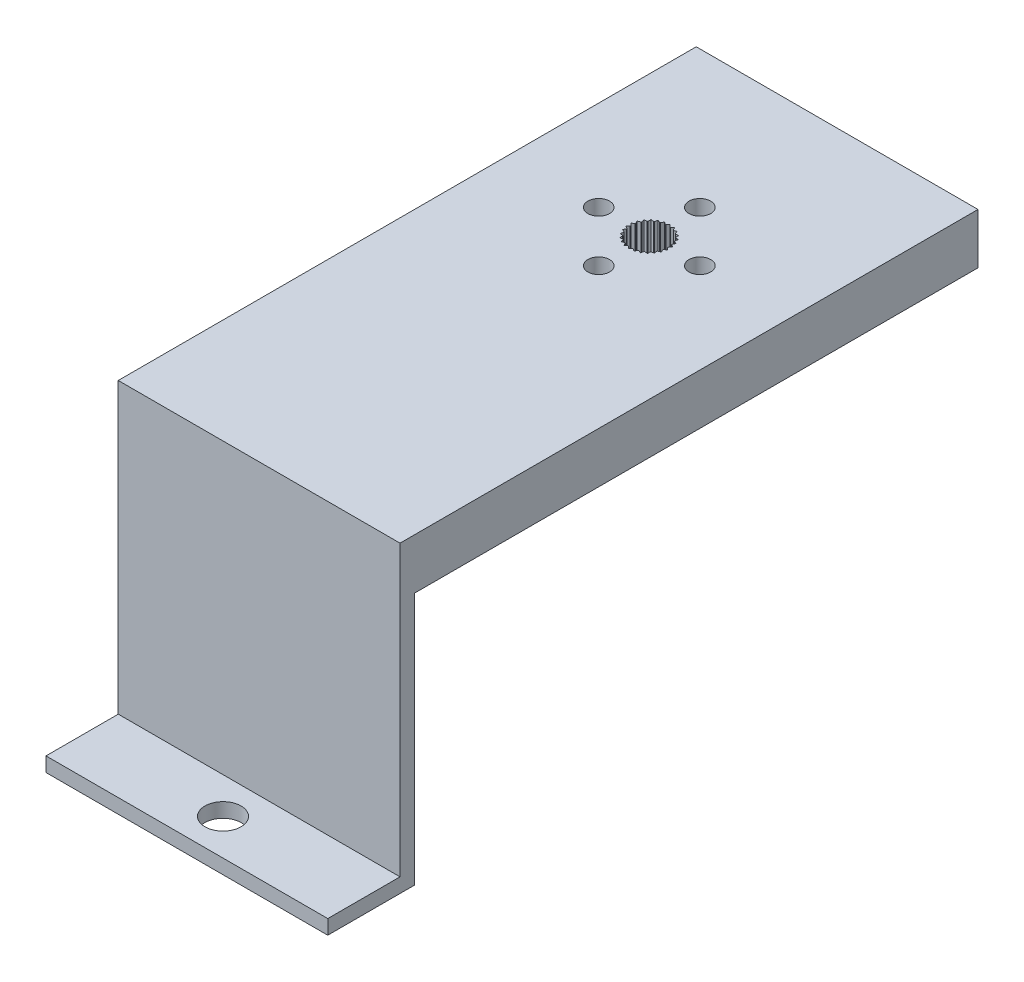
SolidWorks part; units mm, degrees
ref_plane "Front Plane" through (0, 0, 0) normal (0, 0, 1) x (1, 0, 0)
ref_plane "Top Plane" through (0, 0, 0) normal (0, 1, 0) x (1, 0, 0)
ref_plane "Right Plane" through (0, 0, 0) normal (1, 0, 0) x (0, 0, -1)
sketch "Sketch3" plane through (0, 0, 0) normal (1, 0, 0) x (0, 0, -1)
  line L0 (0, 38.5) -> (-60, 38.5)
  line L1 (0, 21.45) -> (0, -21.45) construction
  line L2 (-60, 38.5) -> (-60, 2)
  line L3 (-60, 2) -> (-70, 2)
  line L4 (-70, 2) -> (-70, 0)
  line L5 (21.45, 0) -> (-21.45, 0) construction
  line L6 (-70, 0) -> (-58, 0)
  line L7 (-58, 0) -> (-58, 36.5)
  line L8 (-58, 36.5) -> (0, 36.5)
  line L9 (0, 36.5) -> (0, 38.5)
  dimension "D1" = 70
  dimension "D2" = 38.5
  dimension "D3" = 10
  dimension "D4" = 2
  dimension "D5" = 2
  dimension "D6" = 2
extrude "Boss-Extrude1" add sketch "Sketch3" along normal mid plane 39 contours L2 L3 L4 L6 L7 L8 L9 L0
sketch "Sketch5" plane through (0, 0, 0) normal (0, 1, 0) x (1, 0, 0)
  line L0 (19.5, -58) -> (19.5, 0) construction
  line L1 (0.694, -3.1843) -> (0.3638, -3.4256)
  line L2 (0, -3.1) -> (-0.2629, -3.4133)
  line L3 (0, -3.1) -> (0.2629, -3.4133)
  line L4 (0.694, -3.1843) -> (0.8743, -3.5514)
  line L5 (1.3477, -3.4322) -> (0.9693, -3.5874)
  line L6 (1.3477, -3.4322) -> (1.4349, -3.8318)
  line L7 (1.9231, -3.8293) -> (1.5185, -3.8895)
  line L8 (1.9231, -3.8293) -> (1.9121, -4.2382)
  line L9 (2.3867, -4.3526) -> (1.9794, -4.3142)
  line L10 (2.3867, -4.3526) -> (2.2781, -4.747)
  line L11 (2.7115, -4.9716) -> (2.3254, -4.8369)
  line L12 (2.7115, -4.9716) -> (2.5118, -5.3286)
  line L13 (2.8789, -5.6504) -> (2.5361, -5.4272)
  line L14 (2.8789, -5.6504) -> (2.5995, -5.9492)
  line L15 (2.8789, -6.3496) -> (2.5995, -6.0508)
  line L16 (2.8789, -6.3496) -> (2.5361, -6.5728)
  line L17 (2.7115, -7.0284) -> (2.5118, -6.6714)
  line L18 (2.7115, -7.0284) -> (2.3254, -7.1631)
  line L19 (2.3867, -7.6474) -> (2.2781, -7.253)
  line L20 (2.3867, -7.6474) -> (1.9794, -7.6858)
  line L21 (1.9231, -8.1707) -> (1.9121, -7.7618)
  line L22 (1.9231, -8.1707) -> (1.5185, -8.1105)
  line L23 (1.3477, -8.5678) -> (1.4349, -8.1682)
  line L24 (1.3477, -8.5678) -> (0.9693, -8.4126)
  line L25 (0.694, -8.8157) -> (0.8743, -8.4486)
  line L26 (0.694, -8.8157) -> (0.3638, -8.5744)
  line L27 (0, -8.9) -> (0.2629, -8.5867)
  line L28 (0, -8.9) -> (-0.2629, -8.5867)
  line L29 (-0.694, -8.8157) -> (-0.3638, -8.5744)
  line L30 (-0.694, -8.8157) -> (-0.8743, -8.4486)
  line L31 (-1.3477, -8.5678) -> (-0.9693, -8.4126)
  line L32 (-1.3477, -8.5678) -> (-1.4349, -8.1682)
  line L33 (-1.9231, -8.1707) -> (-1.5185, -8.1105)
  line L34 (-1.9231, -8.1707) -> (-1.9121, -7.7618)
  line L35 (-2.3867, -7.6474) -> (-1.9794, -7.6858)
  line L36 (-2.3867, -7.6474) -> (-2.2781, -7.253)
  line L37 (-2.7115, -7.0284) -> (-2.3254, -7.1631)
  line L38 (-2.7115, -7.0284) -> (-2.5118, -6.6714)
  line L39 (-2.8789, -6.3496) -> (-2.5361, -6.5728)
  line L40 (-2.8789, -6.3496) -> (-2.5995, -6.0508)
  line L41 (-2.8789, -5.6504) -> (-2.5995, -5.9492)
  line L42 (-2.8789, -5.6504) -> (-2.5361, -5.4272)
  line L43 (-2.7115, -4.9716) -> (-2.5118, -5.3286)
  line L44 (-2.7115, -4.9716) -> (-2.3254, -4.8369)
  line L45 (-2.3867, -4.3526) -> (-2.2781, -4.747)
  line L46 (-2.3867, -4.3526) -> (-1.9794, -4.3142)
  line L47 (-1.9231, -3.8293) -> (-1.9121, -4.2382)
  line L48 (-1.9231, -3.8293) -> (-1.5185, -3.8895)
  line L49 (-1.3477, -3.4322) -> (-1.4349, -3.8318)
  line L50 (-1.3477, -3.4322) -> (-0.9693, -3.5874)
  line L51 (-0.694, -3.1843) -> (-0.8743, -3.5514)
  line L52 (-0.694, -3.1843) -> (-0.3638, -3.4256)
  arc A0 (-0.2629, -3.4133) -> (0.2629, -3.4133) centre (0, -6) ccw
  point P81 (0, -6)
  dimension "D1" = 5.2
  dimension "D2" = 6
  dimension "D3" = 19.5
  dimension "D4" = 26
extrude "Cut-Extrude2" cut sketch "Sketch5" along normal blind 40 contours A0 L3 L2 | A0 L52 L51 | A0 L50 L49 | A0 L48 L47 | A0 L46 L45 | A0 L44 L43 | A0 L42 L41 | A0 L40 L39 | A0 L38 L37 | A0 L36 L35 | A0 L34 L33 | A0 L32 L31 | A0 L30 L29 | A0 L28 L27 | A0 L26 L25 | A0 L24 L23 | A0 L22 L21 | A0 L20 L19 | A0 L18 L17 | A0 L16 L15 | A0 L4 L1 | A0 L6 L5 | A0 L8 L7 | A0 L10 L9 | A0 L12 L11 | A0 L14 L13 region at (0.6455, 0, 3.3813) region at (0, 0, 5.9902) region at (1.2534, 0, 3.6119) region at (1.7885, 0, 3.9812) region at (-0.6455, 0, 3.3813) region at (2.2197, 0, 4.4679) region at (-1.2534, 0, 3.6119) region at (2.5218, 0, 5.0436) region at (-1.7885, 0, 3.9812) region at (2.6774, 0, 5.6749) region at (-2.2197, 0, 4.4679) region at (2.6774, 0, 6.3251) region at (-2.5218, 0, 5.0436) region at (2.5218, 0, 6.9564) region at (-2.6774, 0, 5.6749) region at (2.2197, 0, 7.5321) region at (-2.6774, 0, 6.3251) region at (1.7885, 0, 8.0188) region at (-2.5218, 0, 6.9564) region at (1.2534, 0, 8.3881) region at (-2.2197, 0, 7.5321) region at (0.6455, 0, 8.6187) region at (-1.7885, 0, 8.0188) region at (0, 0, 8.6971) region at (-1.2534, 0, 8.3881) region at (-0.6455, 0, 8.6187)
sketch "Sketch7" plane through (0, 0, 0) normal (0, 1, 0) x (1, 0, 0)
  line L1 (-19.5, -58) -> (-14.4, -58)
  line L2 (-19.5, -58) -> (-19.5, -38.2)
  line L3 (-19.5, -38.2) -> (-14.4, -38.2)
  line L4 (-14.4, -58) -> (-14.4, -38.2)
  dimension "D1" = 19.8
  dimension "D2" = 5.1
extrude "Boss-Extrude3" add sketch "Sketch7" along normal up to surface (36.5 mm away) up to face at (0, 36.5, 29)
ref_plane "Plane1" through (0, 40, 0) normal (0, 1, 0) x (1, 0, 0)
sketch "Sketch10" plane through (0, 40, 0) normal (0, 1, 0) x (1, 0, 0)
  line L0 (1.9231, -3.8293) -> (1.5185, -3.8895) construction
  line L1 (1.9231, -3.8293) -> (1.9121, -4.2382) construction
  line L2 (0, -3.1) -> (-0.2629, -3.4133)
  line L3 (0.2629, -3.4133) -> (0, -3.1)
  line L4 (0, -3.1) -> (-0.2629, -3.4133)
  line L5 (0.2629, -3.4133) -> (0, -3.1)
  line L6 (1.3477, -3.4322) -> (0.9693, -3.5874) construction
  line L7 (1.3477, -3.4322) -> (1.4349, -3.8318) construction
  line L8 (0.694, -3.1843) -> (0.3638, -3.4256) construction
  line L9 (0.694, -3.1843) -> (0.8743, -3.5514) construction
  line L10 (2.3867, -7.6474) -> (2.2781, -7.253) construction
  line L11 (2.3867, -7.6474) -> (1.9794, -7.6858) construction
  line L12 (2.7115, -7.0284) -> (2.5118, -6.6714) construction
  line L13 (2.7115, -7.0284) -> (2.3254, -7.1631) construction
  line L14 (2.8789, -6.3496) -> (2.5995, -6.0508) construction
  line L15 (2.8789, -6.3496) -> (2.5361, -6.5728) construction
  line L16 (2.8789, -5.6504) -> (2.5361, -5.4272) construction
  line L17 (2.8789, -5.6504) -> (2.5995, -5.9492) construction
  line L18 (2.7115, -4.9716) -> (2.3254, -4.8369) construction
  line L19 (2.7115, -4.9716) -> (2.5118, -5.3286) construction
  line L20 (2.3867, -4.3526) -> (1.9794, -4.3142) construction
  line L21 (2.3867, -4.3526) -> (2.2781, -4.747) construction
  line L22 (-0.694, -8.8157) -> (-0.3638, -8.5744) construction
  line L23 (-0.694, -8.8157) -> (-0.8743, -8.4486) construction
  line L24 (0, -8.9) -> (0.2629, -8.5867) construction
  line L25 (0, -8.9) -> (-0.2629, -8.5867) construction
  line L26 (0.694, -8.8157) -> (0.8743, -8.4486) construction
  line L27 (0.694, -8.8157) -> (0.3638, -8.5744) construction
  line L28 (1.3477, -8.5678) -> (1.4349, -8.1682) construction
  line L29 (1.3477, -8.5678) -> (0.9693, -8.4126) construction
  line L30 (1.9231, -8.1707) -> (1.9121, -7.7618) construction
  line L31 (1.9231, -8.1707) -> (1.5185, -8.1105) construction
  line L32 (-2.8789, -6.3496) -> (-2.5361, -6.5728) construction
  line L33 (-2.8789, -6.3496) -> (-2.5995, -6.0508) construction
  line L34 (-2.7115, -7.0284) -> (-2.3254, -7.1631) construction
  line L35 (-2.7115, -7.0284) -> (-2.5118, -6.6714) construction
  line L36 (-2.3867, -7.6474) -> (-1.9794, -7.6858) construction
  line L37 (-2.3867, -7.6474) -> (-2.2781, -7.253) construction
  line L38 (-1.9231, -8.1707) -> (-1.5185, -8.1105) construction
  line L39 (-1.9231, -8.1707) -> (-1.9121, -7.7618) construction
  line L40 (-1.3477, -8.5678) -> (-0.9693, -8.4126) construction
  line L41 (-1.3477, -8.5678) -> (-1.4349, -8.1682) construction
  line L42 (-0.694, -3.1843) -> (-0.8743, -3.5514) construction
  line L43 (-0.694, -3.1843) -> (-0.3638, -3.4256) construction
  line L44 (-1.3477, -3.4322) -> (-1.4349, -3.8318) construction
  line L45 (-1.3477, -3.4322) -> (-0.9693, -3.5874) construction
  line L46 (-1.9231, -3.8293) -> (-1.9121, -4.2382) construction
  line L47 (-1.9231, -3.8293) -> (-1.5185, -3.8895) construction
  line L48 (-2.3867, -4.3526) -> (-2.2781, -4.747) construction
  line L49 (-2.3867, -4.3526) -> (-1.9794, -4.3142) construction
  line L50 (-2.7115, -4.9716) -> (-2.5118, -5.3286) construction
  line L51 (-2.7115, -4.9716) -> (-2.3254, -4.8369) construction
  line L52 (-2.8789, -5.6504) -> (-2.5995, -5.9492) construction
  line L53 (-2.8789, -5.6504) -> (-2.5361, -5.4272) construction
  line L54 (1.9231, -3.8293) -> (1.5185, -3.8895)
  line L55 (1.9231, -3.8293) -> (1.9121, -4.2382)
  line L56 (1.3477, -3.4322) -> (0.9693, -3.5874)
  line L57 (1.3477, -3.4322) -> (1.4349, -3.8318)
  line L58 (0.694, -3.1843) -> (0.3638, -3.4256)
  line L59 (0.694, -3.1843) -> (0.8743, -3.5514)
  line L60 (2.3867, -7.6474) -> (2.2781, -7.253)
  line L61 (2.3867, -7.6474) -> (1.9794, -7.6858)
  line L62 (2.7115, -7.0284) -> (2.5118, -6.6714)
  line L63 (2.7115, -7.0284) -> (2.3254, -7.1631)
  line L64 (2.8789, -6.3496) -> (2.5995, -6.0508)
  line L65 (2.8789, -6.3496) -> (2.5361, -6.5728)
  line L66 (2.8789, -5.6504) -> (2.5361, -5.4272)
  line L67 (2.8789, -5.6504) -> (2.5995, -5.9492)
  line L68 (2.7115, -4.9716) -> (2.3254, -4.8369)
  line L69 (2.7115, -4.9716) -> (2.5118, -5.3286)
  line L70 (2.3867, -4.3526) -> (1.9794, -4.3142)
  line L71 (2.3867, -4.3526) -> (2.2781, -4.747)
  line L72 (-0.694, -8.8157) -> (-0.3638, -8.5744)
  line L73 (-0.694, -8.8157) -> (-0.8743, -8.4486)
  line L74 (0, -8.9) -> (0.2629, -8.5867)
  line L75 (0, -8.9) -> (-0.2629, -8.5867)
  line L76 (0.694, -8.8157) -> (0.8743, -8.4486)
  line L77 (0.694, -8.8157) -> (0.3638, -8.5744)
  line L78 (1.3477, -8.5678) -> (1.4349, -8.1682)
  line L79 (1.3477, -8.5678) -> (0.9693, -8.4126)
  line L80 (1.9231, -8.1707) -> (1.9121, -7.7618)
  line L81 (1.9231, -8.1707) -> (1.5185, -8.1105)
  line L82 (-2.8789, -6.3496) -> (-2.5361, -6.5728)
  line L83 (-2.8789, -6.3496) -> (-2.5995, -6.0508)
  line L84 (-2.7115, -7.0284) -> (-2.3254, -7.1631)
  line L85 (-2.7115, -7.0284) -> (-2.5118, -6.6714)
  line L86 (-2.3867, -7.6474) -> (-1.9794, -7.6858)
  line L87 (-2.3867, -7.6474) -> (-2.2781, -7.253)
  line L88 (-1.9231, -8.1707) -> (-1.5185, -8.1105)
  line L89 (-1.9231, -8.1707) -> (-1.9121, -7.7618)
  line L90 (-1.3477, -8.5678) -> (-0.9693, -8.4126)
  line L91 (-1.3477, -8.5678) -> (-1.4349, -8.1682)
  line L92 (-0.694, -3.1843) -> (-0.8743, -3.5514)
  line L93 (-0.694, -3.1843) -> (-0.3638, -3.4256)
  line L94 (-1.3477, -3.4322) -> (-1.4349, -3.8318)
  line L95 (-1.3477, -3.4322) -> (-0.9693, -3.5874)
  line L96 (-1.9231, -3.8293) -> (-1.9121, -4.2382)
  line L97 (-1.9231, -3.8293) -> (-1.5185, -3.8895)
  line L98 (-2.3867, -4.3526) -> (-2.2781, -4.747)
  line L99 (-2.3867, -4.3526) -> (-1.9794, -4.3142)
  line L100 (-2.7115, -4.9716) -> (-2.5118, -5.3286)
  line L101 (-2.7115, -4.9716) -> (-2.3254, -4.8369)
  line L102 (-2.8789, -5.6504) -> (-2.5995, -5.9492)
  line L103 (-2.8789, -5.6504) -> (-2.5361, -5.4272)
  line L108 (-19.5, 0) -> (-19.5, -60)
  line L109 (-19.5, -60) -> (19.5, -60)
  line L110 (19.5, -60) -> (19.5, 0)
  line L111 (19.5, 0) -> (-19.5, 0)
  line L112 (-19.5, 0) -> (-19.5, -60)
  line L113 (-19.5, -60) -> (19.5, -60)
  line L114 (19.5, -60) -> (19.5, 0)
  line L115 (19.5, 0) -> (-19.5, 0)
  arc A1 (-0.2629, -3.4133) -> (0.2629, -3.4133) centre (0, -6) ccw
  arc A2 (-0.2629, -3.4133) -> (0.2629, -3.4133) centre (0, -6) ccw
  dimension "D1" = 0
  dimension "D2" = 0
extrude "Boss-Extrude6" add sketch "Sketch10" against normal blind 5 and the other way blind 2 contours L114 L115 L112 L113 A2 L58 L59 L56 L57 L54 L55 L70 L71 L68 L69 L66 L67 L64 L65 L62 L63 L60 L61 L80 L81 L78 L79 L76 L77 L74 L75 L72 L73 L90 L91 region at (0, 40, 30.2409)
sketch "Sketch14" plane through (0, 0, 0) normal (0, 1, 0) x (1, 0, 0)
  line L0 (19.5, -70) -> (-19.5, -70) construction
  circle A0 centre (0, -65) radius 2.5
  dimension "D1" = 5
  dimension "D2" = 5
ref_plane "Plane2" through (0, 42, 0) normal (0, 1, 0) x (1, 0, 0)
extrude "Cut-Extrude4" cut sketch "Sketch14" along normal blind 5
sketch "Sketch20" plane through (0, 0, 0) normal (0, 0, -1) x (-1, 0, 0)
  line L0 (17.6962, 42) -> (-17.6962, 42) construction
  line L1 (19.5, 35) -> (-19.5, 35)
  line L2 (-19.5, 35) -> (-19.5, 42)
  line L3 (-19.5, 42) -> (19.5, 42)
  line L4 (19.5, 35) -> (19.5, 42)
  line L5 (19.5, 35) -> (19.5, 42) construction
extrude "Boss-Extrude7" add sketch "Sketch20" along normal blind 20
sketch "Sketch21" plane through (0, 42, 0) normal (0, 1, 0) x (1, 0, 0)
  circle A0 centre (0, -13) radius 1.5
  circle A1 centre (-7, -6) radius 1.5
  circle A2 centre (0, 1) radius 1.5
  circle A3 centre (7, -6) radius 1.5
  point P2 (0, -6)
  point P13 (0, -6)
  dimension "D2" = 3
  dimension "D1" = 7
  dimension "D3" = 4
extrude "Cut-Extrude10" cut sketch "Sketch21" against normal through all both and the other way through all
sketch "Sketch22" plane through (-19.5, 0, 0) normal (-1, 0, 0) x (0, 0, 1)
  line L0 (60, 42) -> (60, 2) construction
  line L1 (58, 12) -> (38.2, 12)
  line L2 (58, 12) -> (58, 35)
  line L3 (58, 35) -> (38.2, 35)
  line L4 (38.2, 12) -> (38.2, 35)
  line L5 (70, 0) -> (38.2, 0) construction
  dimension "D1" = 2
  dimension "D2" = 12
extrude "Cut-Extrude11" cut sketch "Sketch22" against normal through all both and the other way through all
